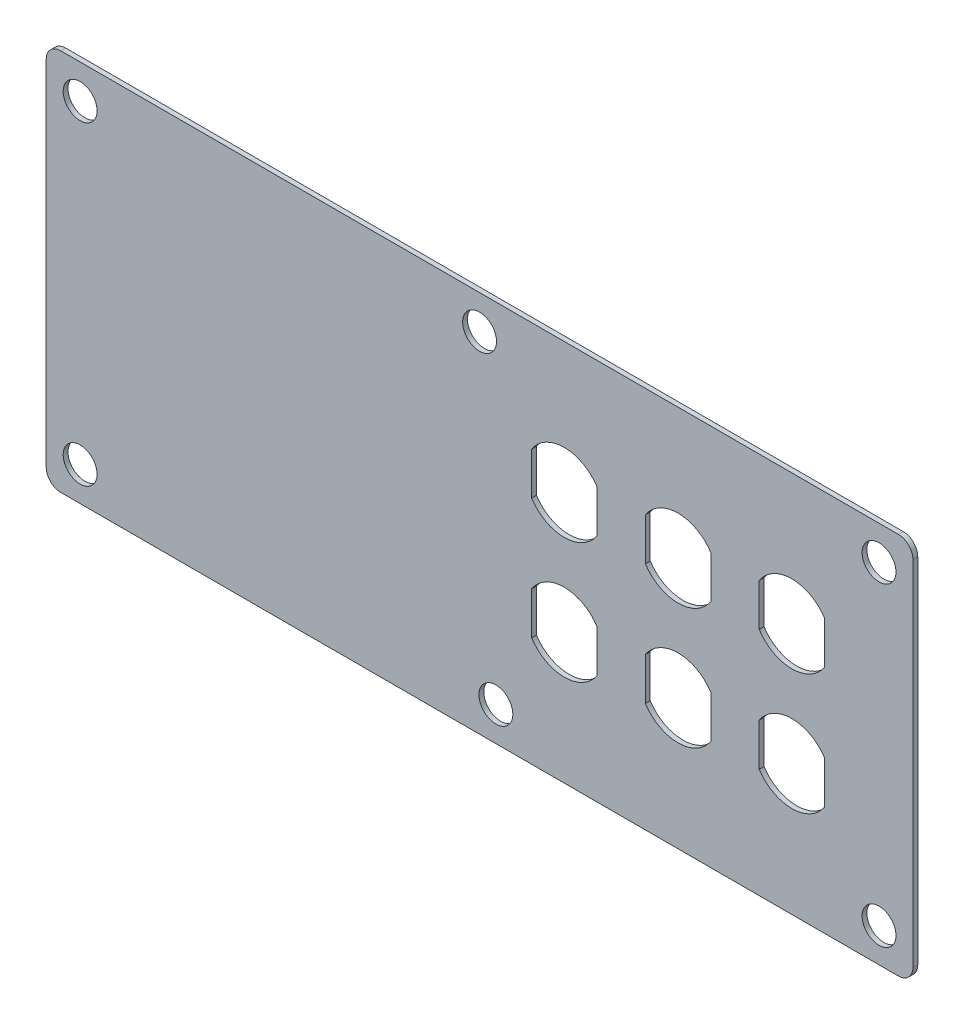
SolidWorks part; units mm, degrees
material "AISI Type 316L stainless steel"
ref_plane "Front Plane" through (0, 0, 0) normal (0, 0, 1) x (1, 0, 0)
ref_plane "Top Plane" through (0, 0, 0) normal (0, 1, 0) x (1, 0, 0)
ref_plane "Right Plane" through (0, 0, 0) normal (1, 0, 0) x (0, 0, -1)
sketch "Sketch1" plane through (0, 0, 0) normal (0, 0, 1) x (1, 0, 0)
  line L0 (0, 0) -> (0, 16.6945) construction
  line L1 (0, 0) -> (42, 0) construction
  line L2 (0, 0) -> (14, 24.2487) construction
  line L3 (14, 24.2487) -> (28, 0) construction
  line L4 (42, 24.2487) -> (42, 0) construction
  line L5 (-6.75, -4.3863) -> (-6.75, 4.3863)
  line L6 (-47.5, -27.375) -> (131.5, -27.375)
  line L7 (-47.5, -27.375) -> (-47.5, 51.6237)
  line L8 (-47.5, 51.6237) -> (131.5, 51.6237)
  line L9 (131.5, -27.375) -> (131.5, 51.6237)
  line L10 (-47.5, -27.375) -> (131.5, 51.6237) construction
  line L11 (-47.5, 51.6237) -> (131.5, -27.375) construction
  line L12 (6.75, 4.3863) -> (6.75, -4.3863)
  line L13 (-6.75, 0) -> (0, 0) construction
  line L14 (0, 0) -> (6.75, 0) construction
  circle A0 centre (0, 0) radius 12.5 construction
  arc A1 (6.75, 4.3863) -> (-6.75, 4.3863) centre (0, 0) ccw
  circle A2 centre (28, 0) radius 8.05 construction
  circle A3 centre (28, 0) radius 12.5 construction
  circle A4 centre (56, 0) radius 8.05 construction
  circle A5 centre (56, 0) radius 12.5 construction
  circle A6 centre (84, 0) radius 8.05 construction
  circle A7 centre (84, 0) radius 12.5 construction
  circle A8 centre (14, 24.2487) radius 12.5 construction
  circle A9 centre (14, 24.2487) radius 8.05 construction
  circle A10 centre (42, 24.2487) radius 12.5 construction
  circle A11 centre (42, 24.2487) radius 8.05 construction
  circle A12 centre (70, 24.2487) radius 12.5 construction
  circle A13 centre (70, 24.2487) radius 8.05 construction
  circle A14 centre (99.4975, 21.9244) radius 12.5 construction
  arc A15 (-6.75, -4.3863) -> (6.75, -4.3863) centre (0, 0) ccw
  point P19 (14, 36.7487)
  point P25 (42, 12.1244)
  point P30 (-12.5, 0)
  dimension "D1" = 25
  dimension "D2" = 16.1
  dimension "D10" = 25
  dimension "D4" = 28
  dimension "D6" = 14
  dimension "D7" = 42
  dimension "D8" = 14.875
  dimension "D9" = 35
  dimension "D11" = 13.5
  dimension "D3" = 4
  dimension "D5" = 3
extrude "Boss-Extrude1" add sketch "Sketch1" along normal blind 1 contours L5 A15 L12 A1 | L6 L9 L8 L7 A15 L5 A1 L12 region at (0, 0, 0) region at (42.5663, 12.2878, 0)
fillet "Fillet1" radius 3 4 edges at (131.5, -27.375, 0.5) (-47.5, -27.375, 0.5) (-47.5, 51.6237, 0.5) (131.5, 51.6237, 0.5)
sketch "Sketch4" plane through (0, 0, 1) normal (0, 0, 1) x (1, 0, 0)
  line L3 (131.5, -24.375) -> (131.5, 48.6237) construction
  line L14 (113.25, 29.0101) -> (113.25, 20.2374)
  line L15 (99.75, 29.0101) -> (99.75, 20.2374)
  line L16 (-44.5, 51.6237) -> (128.5, 51.6237) construction
  arc A9 (113.25, 29.0101) -> (99.75, 29.0101) centre (106.5, 24.6237) ccw
  arc A10 (99.75, 20.2374) -> (113.25, 20.2374) centre (106.5, 24.6237) ccw
  dimension "D3" = 16.1
  dimension "D4" = 13.5
  dimension "D5" = 27
  dimension "D1" = 25
extrude "Cut-Extrude1" cut sketch "Sketch4" against normal through all contours L14 A10 L15 A9
hole_wizard "Ø7.0 (7) Diameter Hole1" positions "Sketch2" profile "Sketch3" hole size "Ø7.0" standard "ISO" end condition through all
sketch "Sketch2" plane through (0, 0, 1) normal (0, 0, 1) x (1, 0, 0)
  line L0 (42, 51.6237) -> (42, 44.6237) construction
  line L3 (-40.5, -20.375) -> (-40.5, 44.6237) construction
  line L4 (-40.5, 44.6237) -> (42, 44.6237) construction
  line L5 (42, 44.6237) -> (124.5, 44.6237) construction
  line L6 (124.5, 44.6237) -> (124.5, -20.375) construction
  line L7 (124.5, -20.375) -> (45.365, -20.375) construction
  line L8 (45.365, -20.375) -> (-40.5, -20.375) construction
  line L11 (-40.5, 12.1244) -> (-47.5, 12.1244) construction
  line L12 (-47.5, -24.375) -> (-47.5, 48.6237) construction
  line L13 (-44.5, 51.6237) -> (128.5, 51.6237) construction
  point P0 (42, 44.6237)
  point P9 (-40.5, 44.6237)
  point P11 (124.5, 44.6237)
  point P13 (124.5, -20.375)
  point P15 (45.365, -20.375)
  point P17 (-40.5, -20.375)
  dimension "D1" = 7
  dimension "D2" = 7
sketch "Sketch3" plane through (42, 44.6237, 1) normal (1, 0, 0) x (0, -1, 0)
  line L0 (0, 0) -> (0, 1)
  line L1 (0, 1) -> (3.5, 1)
  line L2 (3.5, 1) -> (3.5, 0)
  line L5 (3.5, 0) -> (0, 0)
  line L11 (0, -6.35) -> (0, 107.95) construction
  dimension "Thru Hole Dia." = 7
  dimension "Thru Hole Depth" = 1
ref_plane "Plane1" through (42, 0, 0) normal (-1, 0, 0) x (0, 0, 1)
ref_plane "Plane2" through (0, 12.1244, 0) normal (0, 1, 0) x (1, 0, 0)
mirror "Mirror1" about plane through (0, 12.1244, 0) normal (0, 1, 0) of "Cut-Extrude1"
pattern_linear "LPattern1" count 3 spacing 23.5 along (-1, 0, 0) of "Mirror1", "Cut-Extrude1"
sketch "Sketch5" plane through (0, 0, 0) normal (0, 0, -1) x (-1, 0, 0)
  circle A0 centre (-106.5, 24.6237) radius 10.45 construction
  circle A1 centre (-83, 24.6237) radius 10.45 construction
  dimension "D1" = 20.9
